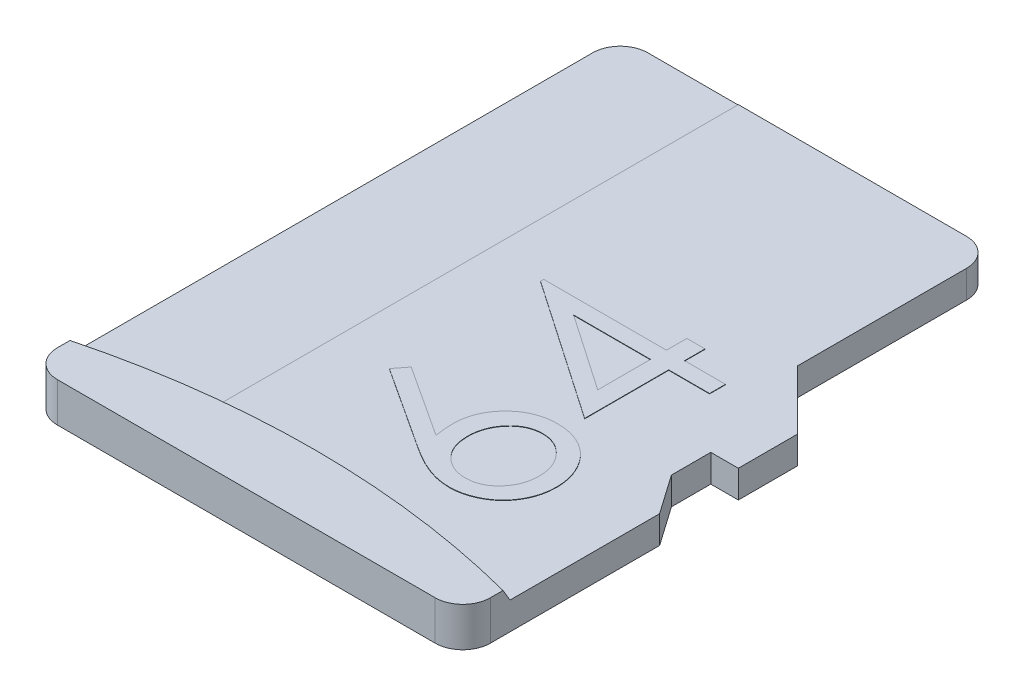
SolidWorks part; units mm, degrees
ref_plane "Front Plane" through (0, 0, 0) normal (0, 0, 1) x (1, 0, 0)
ref_plane "Top Plane" through (0, 0, 0) normal (0, 1, 0) x (1, 0, 0)
ref_plane "Right Plane" through (0, 0, 0) normal (1, 0, 0) x (0, 0, -1)
sketch "Sketch1" plane through (0, 0, 0) normal (0, 1, 0) x (1, 0, 0)
  line L0 (4.5, 2.5) -> (6, 1)
  line L1 (-5, 7.5) -> (4.5, 7.5)
  line L2 (-5, 7.5) -> (-5, -7.5)
  line L3 (-5, -7.5) -> (6, -7.5)
  line L4 (6, 1) -> (6, -0.5)
  line L6 (4.5, 7.5) -> (4.5, 2.5)
  line L9 (6, 1) -> (6, -0.5)
  line L10 (6, -0.5) -> (5.3, -0.5)
  line L11 (5.3, -0.5) -> (5.3, -1.5)
  line L12 (5.3, -1.5) -> (6, -2.5)
  line L13 (6, -2.5) -> (6, -7.5)
  dimension "D1" = 9.5
  dimension "D2" = 11
  dimension "D3" = 15
  dimension "D4" = 1.5
  dimension "D5" = 1
  dimension "D6" = 1
  dimension "D7" = 1.5
  dimension "D8" = 5
  dimension "D9" = 5
  dimension "D10" = 7.5
  dimension "D11" = 0.7
extrude "Boss-Extrude1" add sketch "Sketch1" along normal blind 0.7 contours L13 L12 L11 L10 L4 L0 L6 L1 L2 L3 region at (0.1994, 0, 0.2473)
sketch "Sketch2" plane through (0, 0.7, 0) normal (0, 1, 0) x (1, 0, 0)
  line L0 (-5, 7.5) -> (-5, -7.5) construction
  line L1 (6, -2.5) -> (6, -7.5) construction
  line L2 (-5, -7.5) -> (6, -7.5) construction
  line L3 (-5, -6.3) -> (-5, -7.5)
  line L4 (-5, -7.5) -> (6, -7.5)
  line L5 (6, -7.5) -> (6, -6.3)
  arc A0 (-5, -6.3) -> (6, -6.3) centre (0.5, -27.5571) cw
  point P3 (0.5, -5.6)
  dimension "D1" = 0.7
  dimension "D2" = 1.2
  dimension "D3" = 1.2
extrude "Boss-Extrude2" add sketch "Sketch2" along normal blind 0.3
fillet "Fillet1" radius 0.7 4 edges at (-5, 0.35, -7.5) (4.5, 0.35, -7.5) (-5, 0.5, 7.5) (6, 0.5, 7.5)
chamfer "Chamfer1" distance 0.3 angle 30 1 edges at (0.5, 1, 5.6) first distance on face at (0.5, 0.85, 5.95)
sketch "Sketch3" plane through (0, 0, 0) normal (0, -1, 0) x (1, 0, 0)
  line L0 (-4.3, -7.5) -> (3.8, -7.5) construction
  line L1 (-4.2, -3.5) -> (-3.4, -3.5)
  line L2 (-4.2, -3.5) -> (-4.2, -6.5)
  line L3 (-4.2, -6.5) -> (-3.4, -6.5)
  line L4 (-3.4, -3.5) -> (-3.4, -6.5)
  line L5 (-5, -6.8) -> (-5, 6.8) construction
  dimension "D1" = 0.8
  dimension "D2" = 3
  dimension "D3" = 1
  dimension "D4" = 0.8
extrude "Boss-Extrude3" add sketch "Sketch3" along normal blind 0.01
pattern_linear "LPattern1" count 8 spacing 1 along (1, 0, 0) of "Boss-Extrude3"
sketch "Sketch4" plane through (0, 0.7, 0) normal (0, 1, 0) x (1, 0, 0)
  line L0 (4, 4.0687) -> (4, -5) construction
  line L1 (6, -2.5) -> (6, -6.3) construction
  line L2 (-4.3, -7.5) -> (5.3, -7.5) construction
  text T0 "64" font "Century Gothic" height 4.5
  dimension "D1" = 2
  dimension "D2" = 2.5
sketch "Sketch5" plane through (0, 0.7, 0) normal (0, 1, 0) x (1, 0, 0)
  line L1 (-5, -6.3) -> (-5, 7.6876)
  line L2 (-5, 7.6876) -> (-2, 7.6876)
  line L3 (-2, 7.6876) -> (-2, -5.7428)
  arc A0 (-5, -6.3) -> (-2, -5.7428) centre (0.5, -27.5571) cw
  dimension "D1" = 3
extrude "Cut-Extrude1" cut sketch "Sketch5" against normal blind 0.01
extrude "Boss-Extrude4" add sketch "Sketch4" along normal blind 0.01
